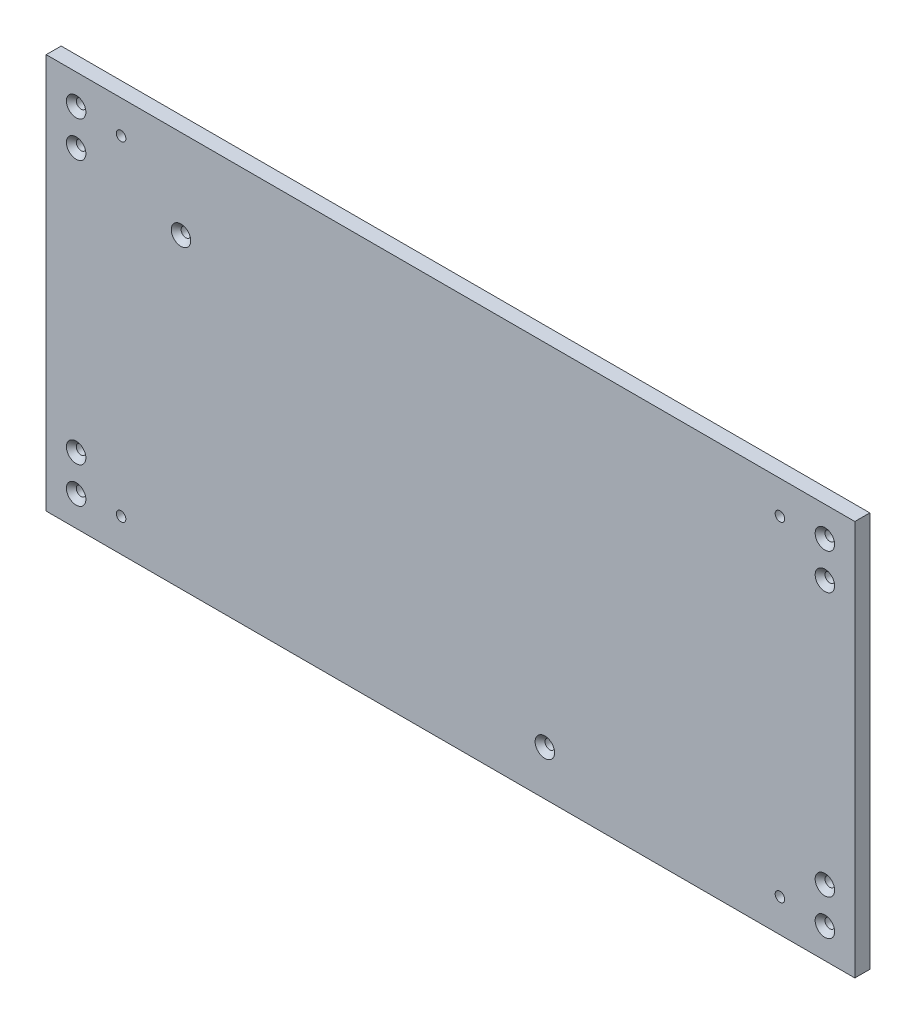
SolidWorks part; units mm, degrees
material "Polycarbonate (PC)"
ref_plane "Front Plane" through (0, 0, 0) normal (0, 0, 1) x (1, 0, 0)
ref_plane "Top Plane" through (0, 0, 0) normal (0, 1, 0) x (1, 0, 0)
ref_plane "Right Plane" through (0, 0, 0) normal (1, 0, 0) x (0, 0, -1)
sketch "Sketch1" plane through (0, 0, 0) normal (0, 0, 1) x (1, 0, 0)
  line L1 (135, -66) -> (-135, -66)
  line L2 (135, -66) -> (135, 66)
  line L3 (135, 66) -> (-135, 66)
  line L4 (-135, -66) -> (-135, 66)
  line L5 (135, -66) -> (-135, 66) construction
  line L6 (135, 66) -> (-135, -66) construction
  point P0 (0, 0)
  dimension "D1" = 270
  dimension "D2" = 132
extrude "Sheet" add sketch "Sketch1" along normal mid plane 5 contours L4 L1 L2 L3 region at (0, 0, 0)
hole_wizard "Ø3.2 (3.2) WallMountHoles" positions "Sketch6" profile "Sketch7" hole size "Ø3.2" standard "ANSI Metric" end condition through all
sketch "Sketch6" plane through (0, 0, 2.5) normal (0, 0, 1) x (1, 0, 0)
  line L0 (135, 66) -> (-135, 66) construction
  line L1 (-135, -66) -> (-135, 66) construction
  line L4 (135, -66) -> (135, 66) construction
  line L5 (135, -66) -> (-135, -66) construction
  point P0 (-125, 56)
  point P2 (-125, 44)
  point P4 (-125, -44)
  point P6 (-125, -56)
  point P8 (125, -56)
  point P10 (125, -44)
  point P12 (125, 44)
  point P14 (125, 56)
  dimension "D1" = 10
  dimension "D2" = 22
  dimension "D4" = 10
  dimension "D3" = 10
  dimension "D5" = 10
  dimension "D6" = 22
sketch "Sketch7" plane through (-125, 56, 2.5) normal (1, 0, 0) x (0, -1, 0)
  line L0 (0, 0) -> (0, 5)
  line L1 (0, 5) -> (1.6, 5)
  line L2 (1.6, 5) -> (1.6, 1.65)
  line L3 (1.6, 1.65) -> (3.25, 0)
  line L5 (3.25, 0) -> (0, 0)
  line L6 (-1.6, 1.65) -> (-3.25, 0) construction
  line L11 (0, -6.35) -> (0, 107.95) construction
  dimension "Thru Hole Dia." = 3.2
  dimension "Thru Hole Depth" = 5
  dimension "Near C'Sink Dia." = 6.5
  dimension "Near C'Sink Angle" = 90
hole_wizard "Ø3.2 (3.2) FeetMountHoles" positions "Sketch9" profile "Sketch8" hole size "Ø3.2" standard "ANSI Metric" end condition through all
sketch "Sketch9" plane through (0, 0, 2.5) normal (0, 0, 1) x (1, 0, 0)
  line L0 (135, -66) -> (-135, -66) construction
  line L1 (135, -66) -> (135, 66) construction
  point P0 (110, 55)
  point P2 (-110, 55)
  point P4 (-110, -55)
  point P6 (110, -55)
  dimension "D1" = 220
  dimension "D2" = 110
  dimension "D3" = 11
  dimension "D4" = 25
sketch "Sketch8" plane through (110, 55, 2.5) normal (1, 0, 0) x (0, -1, 0)
  line L0 (0, 0) -> (0, 5)
  line L1 (0, 5) -> (1.6, 5)
  line L2 (1.6, 5) -> (1.6, 0)
  line L5 (1.6, 0) -> (0, 0)
  line L11 (0, -6.35) -> (0, 107.95) construction
  dimension "Thru Hole Dia." = 3.2
  dimension "Thru Hole Depth" = 5
hole_wizard "Ø3.2 (3.2) PSUHoles" positions "Sketch10" profile "Sketch11" hole size "Ø3.2" standard "ANSI Metric" end condition through all
sketch "Sketch10" plane through (0, 0, 2.5) normal (0, 0, 1) x (1, 0, 0)
  line L0 (135, -66) -> (-135, -66) construction
  line L2 (-135, -66) -> (-135, 66) construction
  point P0 (31.5, -51)
  point P2 (-90, 36.3)
  dimension "D1" = 121.5
  dimension "D2" = 87.3
  dimension "D3" = 15
  dimension "D4" = 45
sketch "Sketch11" plane through (31.5, -51, 2.5) normal (1, 0, 0) x (0, -1, 0)
  line L0 (0, 0) -> (0, 5)
  line L1 (0, 5) -> (1.6, 5)
  line L2 (1.6, 5) -> (1.6, 1.65)
  line L3 (1.6, 1.65) -> (3.25, 0)
  line L5 (3.25, 0) -> (0, 0)
  line L6 (-1.6, 1.65) -> (-3.25, 0) construction
  line L11 (0, -6.35) -> (0, 107.95) construction
  dimension "Thru Hole Dia." = 3.2
  dimension "Thru Hole Depth" = 5
  dimension "Near C'Sink Dia." = 6.5
  dimension "Near C'Sink Angle" = 90
equation "\"D3@Sketch6\"=\"D4@Sketch6\""
equation "\"D5@Sketch6\"=\"D1@Sketch6\""
equation "\"D6@Sketch6\"=\"D2@Sketch6\""
equation "\"D3@Sketch9\"=(\"D2@Sketch1\"-\"D2@Sketch9\")/2"
equation "\"D4@Sketch9\"=(\"D1@Sketch1\"-\"D1@Sketch9\")/2"
